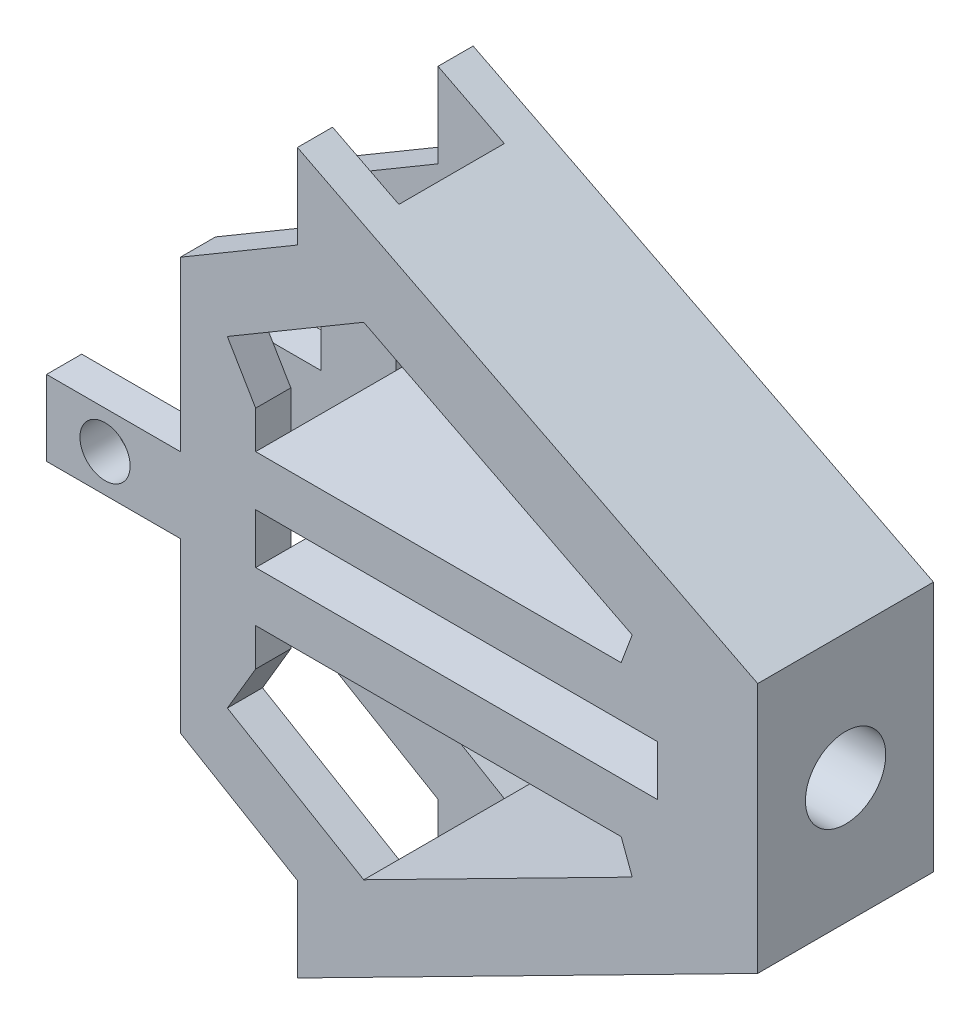
SolidWorks part; units mm, degrees
ref_plane "前视基准面" through (0, 0, 0) normal (0, 0, 1) x (1, 0, 0)
ref_plane "上视基准面" through (0, 0, 0) normal (0, 1, 0) x (1, 0, 0)
ref_plane "右视基准面" through (0, 0, 0) normal (1, 0, 0) x (0, 0, -1)
sketch "草图1" plane through (0, 0, 0) normal (0, 0, 1) x (1, 0, 0)
  line L12 (66, -1) -> (66, 1)
  line L13 (69, -5) -> (40, -19.75)
  line L14 (40, -19.75) -> (37, -19.75)
  line L15 (34.5, -16.75) -> (36.5, -16.75)
  line L16 (31, -16.75) -> (31, -19.75)
  line L17 (34, 13) -> (34, 2.5)
  line L18 (34, 13) -> (31, 16.75)
  line L19 (31, 19.75) -> (34, 19.75)
  line L20 (34, 19.75) -> (34, 17.25)
  line L21 (34.5, 16.75) -> (36.5, 16.75)
  line L22 (37, 13) -> (37, 1.5)
  line L23 (34, -19.75) -> (31, -19.75)
  line L24 (34, -13) -> (31, -16.75)
  line L25 (34, -19.75) -> (34, -17.25)
  line L26 (42.8383, -14.9406) -> (49, -4.5)
  line L27 (46, -1.5) -> (37, -1.5)
  line L28 (34, -2.5) -> (34, -13)
  line L29 (40, 14.6667) -> (46, 4.5)
  line L30 (46, 4.5) -> (46, 1.5)
  line L31 (63, 1.5) -> (64, 4.1774)
  line L32 (49, -1.5) -> (49, -4.5)
  line L33 (49, 4.5) -> (49, 1.5)
  line L34 (49, 1.5) -> (63, 1.5)
  line L35 (37, -17.25) -> (37, -19.75)
  line L36 (37, -1.5) -> (37, -13)
  line L37 (46, -1.5) -> (46, -4.5)
  line L38 (37, 19.75) -> (37, 17.25)
  line L39 (37, -13) -> (40, -14.6667)
  line L40 (46, -4.5) -> (40, -14.6667)
  line L41 (37, 13) -> (40, 14.6667)
  line L42 (37, 1.5) -> (46, 1.5)
  line L43 (42.8383, 14.9406) -> (64, 4.1774)
  line L44 (42.8383, -14.9406) -> (64, -4.1774)
  line L45 (49, 4.5) -> (42.8383, 14.9406)
  line L46 (66.5, 1.5) -> (69, 1.5)
  line L47 (69, 5) -> (69, 1.5)
  line L48 (63, -1.5) -> (49, -1.5)
  line L49 (37, 19.75) -> (40, 19.75)
  line L50 (40, 19.75) -> (69, 5)
  line L51 (31, 19.75) -> (31, 16.75)
  line L52 (69, -5) -> (69, -1.5)
  line L53 (66.5, -1.5) -> (69, -1.5)
  line L54 (63, -1.5) -> (64, -4.1774)
  line L55 (34, -2.5) -> (19.4926, -2.5)
  line L56 (34, 2.5) -> (19.4926, 2.5)
  line L57 (10, -13.9159) -> (19.4926, -2.5)
  line L58 (10, -19.75) -> (10, -13.9159)
  line L59 (10, -19.75) -> (7, -19.75)
  line L60 (7, -17.25) -> (7, -19.75)
  line L61 (3.5, -16.75) -> (6.5, -16.75)
  line L62 (3, -19.75) -> (3, -17.25)
  line L63 (3, -19.75) -> (0, -19.75)
  line L64 (3, -13.75) -> (7, -13.75)
  line L66 (18.0651, 0) -> (7, -13.75)
  line L67 (3, 13.75) -> (7, 13.75)
  line L68 (0, 19.75) -> (3, 19.75)
  line L69 (3, 19.75) -> (3, 17.25)
  line L70 (6.5, 16.75) -> (3.5, 16.75)
  line L71 (7, 19.75) -> (7, 17.25)
  line L72 (7, 19.75) -> (10, 19.75)
  line L73 (19.4926, 2.5) -> (10, 13.9159)
  line L74 (10, 19.75) -> (10, 13.9159)
  line L75 (7, 13.75) -> (18.0651, 0)
  line L78 (0, 19.75) -> (0, -19.75)
  line L81 (3, 13.75) -> (3, -13.75)
  arc A0 (66, -1) -> (66.5, -1.5) centre (66, -1.5) ccw
  arc A1 (37, -17.25) -> (36.5, -16.75) centre (37, -16.75) ccw
  arc A2 (34.5, -16.75) -> (34, -17.25) centre (34, -16.75) ccw
  arc A3 (34, 17.25) -> (34.5, 16.75) centre (34, 16.75) ccw
  arc A4 (36.5, 16.75) -> (37, 17.25) centre (37, 16.75) ccw
  arc A5 (66.5, 1.5) -> (66, 1) centre (66, 1.5) ccw
  arc A6 (7, -17.25) -> (6.5, -16.75) centre (7, -16.75) ccw
  arc A7 (3, 17.25) -> (3.5, 16.75) centre (3, 16.75) ccw
  arc A8 (6.5, 16.75) -> (7, 17.25) centre (7, 16.75) ccw
  arc A9 (3.5, -16.75) -> (3, -17.25) centre (3, -16.75) ccw
extrude "凸台-拉伸1" add sketch "草图1" along normal blind 4
sketch "草图2" plane through (0, -16.75, 0) normal (0, -1, 0) x (1, 0, 0)
  line L0 (3.5, 4) -> (6.5, 4) construction
  line L1 (3, 4) -> (3, 0) construction
  line L2 (7, 4) -> (7, 0) construction
  circle A0 centre (5, 2) radius 0.9
  dimension "D1" = 1.8
  dimension "D2" = 2
  dimension "D3" = 2
  dimension "D4" = 2
extrude "切除-拉伸1" cut sketch "草图2" against normal blind 52
sketch "草图3" plane through (0, 0, 4) normal (0, 0, 1) x (1, 0, 0)
  line L0 (3, 12.413) -> (3, 13.75)
  line L1 (3, 12.413) -> (0, 10.681)
  line L2 (0, 12.681) -> (0, 10.681)
  line L3 (0, 12.681) -> (3, 13.75)
  line L4 (24, -2.5) -> (24, 2.5)
  line L5 (24, -2.5) -> (22, -2.5)
  line L6 (22, 2.5) -> (22, -2.5)
  line L7 (22, 2.5) -> (24, 2.5)
  line L8 (3, -13.75) -> (3, -12.413)
  line L9 (3, -13.75) -> (0, -12.681)
  line L10 (0, -10.681) -> (0, -12.681)
  line L11 (0, -10.681) -> (3, -12.413)
extrude "凸台-拉伸2" add sketch "草图3" along normal blind 1.5
sketch "草图5" plane through (0, 0, 0) normal (0, 0, 1) x (1, 0, 0)
  line L0 (37, 7.25) -> (44.3771, 7.25)
  line L1 (37, 13) -> (37, 1.5) construction
  line L2 (46, 4.5) -> (40, 14.6667) construction
  line L3 (44.3771, 7.25) -> (50.664, 10.9603)
  line L4 (64, 4.1774) -> (42.8383, 14.9406) construction
  line L5 (37, 5.097) -> (45.6477, 5.097)
  line L6 (45.6477, 5.097) -> (53.3059, 9.6166)
  line L8 (42.8383, 14.9406) -> (49, 4.5) construction
  line L9 (37, 5.097) -> (37, 7.25)
  line L10 (53.3059, 9.6166) -> (50.664, 10.9603)
  line L11 (18.0651, 0) -> (31.8024, 0) construction
  line L12 (37, -5.097) -> (45.6477, -5.097)
  line L13 (37, -5.097) -> (37, -7.25)
  line L14 (37, -7.25) -> (44.3771, -7.25)
  line L15 (44.3771, -7.25) -> (50.664, -10.9603)
  line L16 (53.3059, -9.6166) -> (50.664, -10.9603)
  line L17 (45.6477, -5.097) -> (53.3059, -9.6166)
  dimension "D1" = 2.5
  dimension "D2" = 90
extrude "凸台-拉伸3" add sketch "草图5" along normal blind 4
sketch "草图6" plane through (0, 0, 4) normal (0, 0, 1) x (1, 0, 0)
  line L1 (46, 1.5) -> (46, 8.2078)
  line L2 (50.664, 10.9603) -> (50.664, 14.3261)
  line L3 (50.664, 10.9603) -> (46, 8.2078)
  line L4 (69, 5) -> (40, 19.75) construction
  line L10 (37, 0) -> (71.9391, 0) construction
  line L20 (69, 5) -> (50.664, 14.3261)
  line L21 (69, 5) -> (69, -5)
  line L22 (46, 1.5) -> (46, -1.5)
  line L23 (69, -5) -> (50.664, -14.3261)
  line L24 (50.664, -10.9603) -> (50.664, -14.3261)
  line L25 (50.664, -10.9603) -> (46, -8.2078)
  line L26 (46, -1.5) -> (46, -8.2078)
  line L51 (47.8727, 6.4101) -> (49, 4.5)
  line L52 (53.3059, 9.6166) -> (47.8727, 6.4101)
  line L53 (64, 4.1774) -> (53.3059, 9.6166)
  line L54 (63, 1.5) -> (64, 4.1774)
  line L55 (49, 1.5) -> (63, 1.5)
  line L56 (49, 4.5) -> (49, 1.5)
  line L57 (47.8727, 6.4101) -> (49, 4.5)
  line L58 (53.3059, 9.6166) -> (47.8727, 6.4101)
  line L59 (64, 4.1774) -> (53.3059, 9.6166)
  line L60 (63, 1.5) -> (64, 4.1774)
  line L61 (49, 1.5) -> (63, 1.5)
  line L62 (49, 4.5) -> (49, 1.5)
  line L64 (47.8727, -6.4101) -> (53.3059, -9.6166)
  line L65 (49, -4.5) -> (47.8727, -6.4101)
  line L66 (49, -1.5) -> (49, -4.5)
  line L67 (63, -1.5) -> (49, -1.5)
  line L68 (64, -4.1774) -> (63, -1.5)
  line L69 (53.3059, -9.6166) -> (64, -4.1774)
  line L70 (47.8727, -6.4101) -> (53.3059, -9.6166)
  line L71 (49, -4.5) -> (47.8727, -6.4101)
  line L72 (49, -1.5) -> (49, -4.5)
  line L73 (63, -1.5) -> (49, -1.5)
  line L74 (64, -4.1774) -> (63, -1.5)
  line L75 (53.3059, -9.6166) -> (64, -4.1774)
  point P28 (69, 0)
  point P33 (46, 0)
  dimension "D1" = 0
  dimension "D2" = 0
extrude "凸台-拉伸4" add sketch "草图6" along normal blind 1.5
ref_plane "基准面1" through (0, 0, 2) normal (0, 0, 1) x (1, 0, 0)
mirror "镜向1" about plane through (0, 0, 2) normal (0, 0, 1) of "凸台-拉伸4"
sketch "草图7" plane through (0, 0, 2) normal (0, 0, 1) x (1, 0, 0)
  line L0 (53.3059, 9.6166) -> (53.3059, 26.3392)
  line L1 (49, 4.5) -> (49, 1.5) construction
  line L2 (47.8727, 6.4101) -> (49, 4.5) construction
  line L3 (53.3059, 9.6166) -> (47.8727, 6.4101) construction
  line L4 (49, 4.5) -> (49, 1.5)
  line L5 (47.8727, 6.4101) -> (49, 4.5)
  line L6 (53.3059, 9.6166) -> (47.8727, 6.4101)
  line L7 (69, 0) -> (-15.5758, 0) construction
  line L8 (69, -5) -> (69, 5) construction
  line L9 (49, 1.5) -> (49, -1.5)
  line L10 (53.3059, 26.3392) -> (-8.8887, 26.3392)
  line L11 (-8.8887, 26.3392) -> (-8.8887, -26.3392)
  line L12 (53.3059, -26.3392) -> (-8.8887, -26.3392)
  line L13 (53.3059, -9.6166) -> (53.3059, -26.3392)
  line L14 (53.3059, -9.6166) -> (47.8727, -6.4101)
  line L15 (47.8727, -6.4101) -> (49, -4.5)
  line L16 (49, -4.5) -> (49, -1.5)
  point P18 (-8.8887, 0)
  point P23 (49, 0)
extrude "切除-拉伸2" cut sketch "草图7" against normal mid plane 4
sketch "草图8" plane through (0, 0, 2) normal (0, 0, 1) x (1, 0, 0)
  line L1 (-24.1882, 31.0415) -> (32.5197, 31.0415)
  line L2 (-24.1882, 31.0415) -> (-24.1882, -30.7728)
  line L3 (-24.1882, -30.7728) -> (32.5197, -30.7728)
  line L4 (32.5197, 31.0415) -> (32.5197, -30.7728)
extrude "切除-拉伸3" cut sketch "草图8" along normal blind 10
sketch "草图9" plane through (0, 0, 2) normal (0, 0, 1) x (1, 0, 0)
  line L0 (66.5, -1.5) -> (69, -1.5) construction
  line L1 (66, -1) -> (66, 1) construction
  line L2 (66.5, 1.5) -> (69, 1.5) construction
  line L3 (66.5, -1.5) -> (69, -1.5)
  line L4 (66, -1) -> (66, 1)
  line L5 (66.5, 1.5) -> (69, 1.5)
  line L6 (69, -5) -> (69, 5) construction
  line L7 (69, -1.5) -> (69, 1.5)
  arc A0 (66, -1) -> (66.5, -1.5) centre (66, -1.5) ccw construction
  arc A1 (66.5, 1.5) -> (66, 1) centre (66, 1.5) ccw construction
  arc A2 (66, -1) -> (66.5, -1.5) centre (66, -1.5) ccw
  arc A3 (66.5, 1.5) -> (66, 1) centre (66, 1.5) ccw
extrude "凸台-拉伸5" add sketch "草图9" along normal mid plane 4
sketch "草图10" plane through (69, 0, 0) normal (1, 0, 0) x (0, 0, -1)
  line L0 (1.5, 0) -> (-5.5, 0) construction
  line L1 (1.5, -5) -> (1.5, 5) construction
  line L2 (-5.5, -5) -> (-5.5, 5) construction
  circle A0 centre (-2, 0) radius 1.6
  dimension "D1" = 3.2
sketch "草图11" plane through (0, 0, 2) normal (0, 0, 1) x (1, 0, 0)
  line L0 (50.664, -10.9603) -> (50.664, -14.3261) construction
  line L1 (46, -8.2078) -> (50.664, -10.9603) construction
  line L2 (47.8727, 6.4101) -> (49, 4.5) construction
  line L3 (46, 8.2078) -> (46, -8.2078) construction
  line L4 (50.664, 10.9603) -> (46, 8.2078) construction
  line L5 (69, 5) -> (50.664, 14.3261) construction
  line L6 (50.664, 14.3261) -> (50.664, 10.9603) construction
  line L7 (53.3059, 9.6166) -> (47.8727, 6.4101) construction
  line L8 (50.664, -14.3261) -> (69, -5) construction
  line L9 (47.8727, -6.4101) -> (53.3059, -9.6166) construction
  line L10 (49, -4.5) -> (47.8727, -6.4101) construction
  line L11 (49, -4.5) -> (47.8727, -6.4101)
  line L12 (47.8727, -6.4101) -> (53.3059, -9.6166)
  line L13 (50.664, -14.3261) -> (53.3059, -12.9823)
  line L14 (50.664, -10.9603) -> (50.664, -14.3261)
  line L15 (46, -8.2078) -> (50.664, -10.9603)
  line L16 (47.8727, 6.4101) -> (49, 4.5)
  line L17 (46, 8.2078) -> (46, -8.2078)
  line L18 (50.664, 10.9603) -> (46, 8.2078)
  line L19 (53.3059, 12.9823) -> (50.664, 14.3261)
  line L20 (50.664, 14.3261) -> (50.664, 10.9603)
  line L21 (53.3059, 9.6166) -> (47.8727, 6.4101)
  line L22 (53.3059, 9.6166) -> (53.3059, 12.9823)
  line L23 (53.3059, -9.6166) -> (53.3059, -12.9823)
  line L24 (49, 4.5) -> (49, -4.5)
extrude "切除-拉伸5" cut sketch "草图11" against normal mid plane 4.2
sketch "草图12" plane through (0, 0, 5.5) normal (0, 0, 1) x (1, 0, 0)
  line L0 (43, 0) -> (46, 0) construction
  line L1 (46, 8.2078) -> (46, -8.2078) construction
  line L2 (46, 1.5) -> (40.6702, 1.5)
  line L3 (40.6702, 1.5) -> (40.6702, -1.5)
  line L4 (49, 1.5) -> (63, 1.5) construction
  line L5 (43, 0) -> (40.6702, 0) construction
  line L6 (46, -1.5) -> (40.6702, -1.5)
  line L7 (46, -1.5) -> (46, 1.5)
  circle A0 centre (43, 0) radius 1
  dimension "D1" = 2
  dimension "D2" = 3
extrude "凸台-拉伸6" add sketch "草图12" against normal blind 1.4
mirror "镜向2" about plane through (0, 0, 2) normal (0, 0, 1) of "凸台-拉伸6"
sketch "草图13" plane through (0, 0, 5.5) normal (0, 0, 1) x (1, 0, 0)
  line L0 (69, 0) -> (47.5362, 0) construction
  line L1 (69, -5) -> (69, 5) construction
  line L2 (49, 4.5) -> (49, 1.5) construction
  line L3 (49, 1) -> (65, 1)
  line L4 (49, 1) -> (49, -1)
  line L5 (49, -1) -> (65, -1)
  line L6 (65, 1) -> (65, -1)
  line L7 (49, 1) -> (65, -1) construction
  line L8 (49, -1) -> (65, 1) construction
  point P6 (57, 0)
  dimension "D1" = 2
  dimension "D2" = 4
extrude "切除-拉伸6" cut sketch "草图13" against normal through all
sketch "草图14" plane through (0, 0, 2) normal (0, 0, 1) x (1, 0, 0)
  line L1 (49, 3) -> (63.5603, 3)
  line L2 (40.6702, 0) -> (53.1946, 0) construction
  line L3 (40.6702, 1.5) -> (40.6702, -1.5) construction
  line L4 (49, -3) -> (49, -1.5)
  line L5 (49, -1.5) -> (63, -1.5)
  line L6 (63, -1.5) -> (63.5603, -3)
  line L7 (49, 4.5) -> (49, 1.5)
  line L8 (47.8727, 6.4101) -> (49, 4.5)
  line L9 (53.3059, 9.6166) -> (47.8727, 6.4101)
  line L10 (64, 4.1774) -> (53.3059, 9.6166)
  line L11 (63, 1.5) -> (64, 4.1774)
  line L12 (49, 1.5) -> (63, 1.5)
  line L13 (49, 3) -> (49, 1.5)
  line L17 (63, 1.5) -> (63.5603, 3)
  line L18 (49, 1.5) -> (63, 1.5)
  line L19 (49, -3) -> (63.5603, -3)
  dimension "D2" = 1.5
  dimension "D1" = 0
extrude "凸台-拉伸7" add sketch "草图14" along normal mid plane 7
extrude "切除-拉伸7" cut sketch "草图10" against normal through all contours A0
